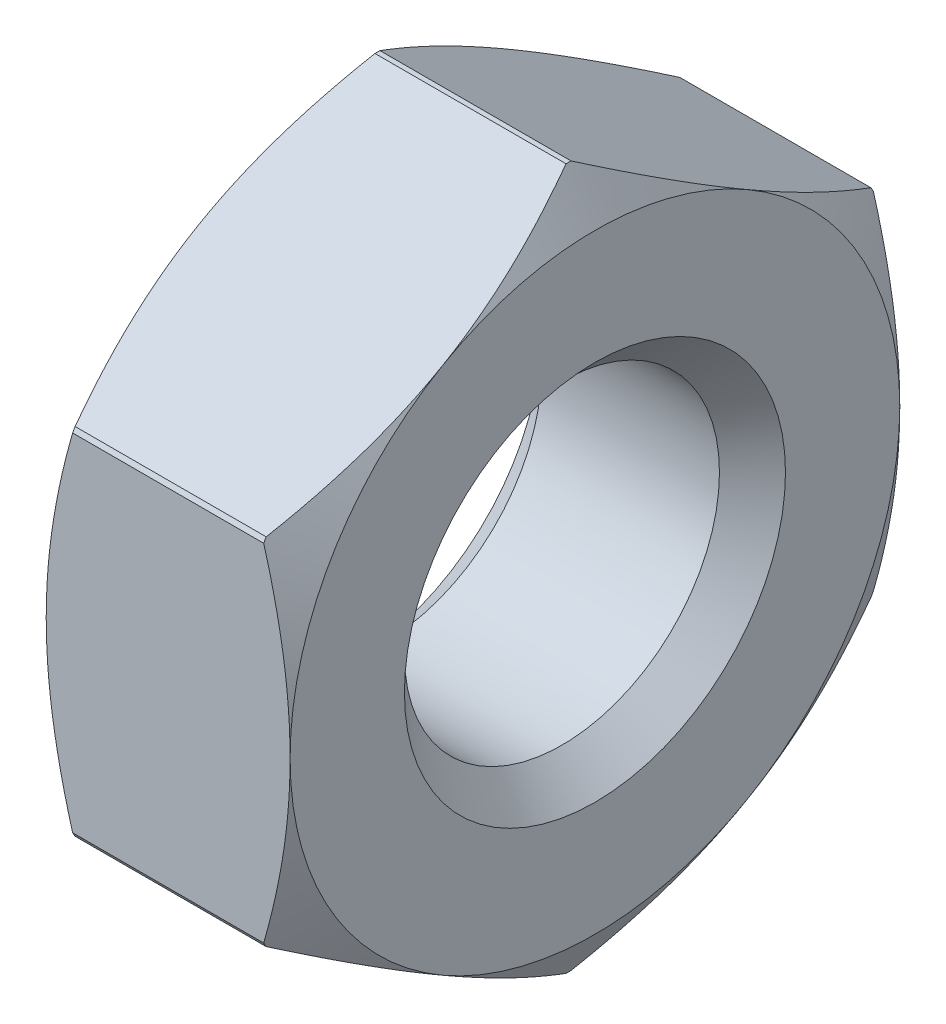
SolidWorks part; units mm, degrees
ref_plane "Front Plane" through (0, 0, 0) normal (0, 0, 1) x (1, 0, 0)
ref_plane "Top Plane" through (0, 0, 0) normal (0, 1, 0) x (1, 0, 0)
ref_plane "Right Plane" through (0, 0, 0) normal (1, 0, 0) x (0, 0, -1)
ref_plane "Plane1" through (0, 0, 0) normal (0, 0, 1) x (1, 0, 0)
sketch "Sketch1" plane through (0, 0, 0) normal (0, 0, 1) x (1, 0, 0)
  line L0 (-1.6, 0) -> (-1.6, 4)
  line L1 (-1.6, 4) -> (-1.2536, 4.6)
  line L2 (-1.2536, 4.6) -> (1.2536, 4.6)
  line L3 (1.2536, 4.6) -> (1.6, 4)
  line L4 (1.6, 4) -> (1.6, 0)
  line L5 (1.6, 0) -> (-1.6, 0)
  line L6 (1.6, 0) -> (-1.6, 0) construction
revolve "Revolve1" add sketch "Sketch1" angle 360 about L6 reverse direction yes
ref_plane "Plane2" through (0, 0, 0) normal (0, 0, 1) x (1, 0, 0)
sketch "Sketch2" plane through (0, 0, 0) normal (0, 0, 1) x (1, 0, 0)
  line L0 (-1.6, 0) -> (-1.6, 2.5)
  line L1 (-1.6, 2.5) -> (-1.167, 2.067)
  line L2 (-1.167, 2.067) -> (1.167, 2.067)
  line L3 (1.167, 2.067) -> (1.6, 2.5)
  line L4 (1.6, 2.5) -> (1.6, 0)
  line L5 (1.6, 0) -> (-1.6, 0)
  line L6 (1.6, 0) -> (-1.6, 0) construction
revolve "Cut-Revolve1" cut sketch "Sketch2" angle 360 about L6 reverse direction yes
ref_plane "Plane3" through (0, 0, 0) normal (1, 0, 0) x (0, 0, -1)
sketch "Sketch3" plane through (0, 0, 0) normal (1, 0, 0) x (0, 0, -1)
  line L0 (-8, 8) -> (-8, -8)
  line L1 (-8, -8) -> (8, -8)
  line L2 (8, -8) -> (8, 8)
  line L3 (8, 8) -> (-8, 8)
  line L4 (-4, 2.3094) -> (-4, -2.3094)
  line L5 (-4, -2.3094) -> (0, -4.6188)
  line L6 (0, -4.6188) -> (4, -2.3094)
  line L7 (4, -2.3094) -> (4, 2.3094)
  line L8 (4, 2.3094) -> (0, 4.6188)
  line L9 (0, 4.6188) -> (-4, 2.3094)
extrude "Cut-Extrude1" cut sketch "Sketch3" against normal blind 1.6 and the other way blind 1.6
